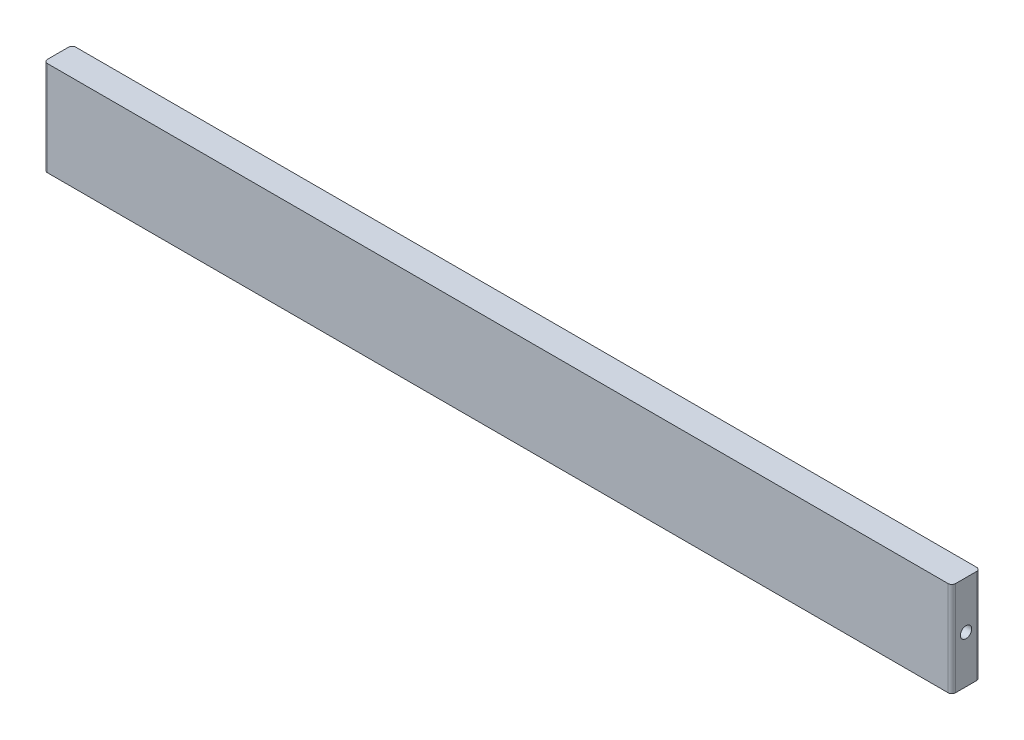
SolidWorks part; units mm, degrees
material "6061 Alloy"
ref_plane "Front Plane" through (0, 0, 0) normal (0, 0, 1) x (1, 0, 0)
ref_plane "Top Plane" through (0, 0, 0) normal (0, 1, 0) x (1, 0, 0)
ref_plane "Right Plane" through (0, 0, 0) normal (1, 0, 0) x (0, 0, -1)
sketch "Sketch1" plane through (0, -21, 0) normal (0, 1, 0) x (1, 0, 0)
  line L0 (-152.4, -170) -> (152.4, -170)
  line L4 (-152.4, 179.525) -> (-152.4, -179.525)
  line L5 (-152.4, -179.525) -> (152.4, -179.525)
  line L7 (152.4, 179.525) -> (-152.4, 179.525)
  line L9 (-152.4, -179.525) -> (152.4, -179.525)
  line L11 (152.4, 179.525) -> (-152.4, 179.525)
  line L17 (-152.4, 179.525) -> (-152.4, -179.525)
  line L23 (152.4, -179.525) -> (152.4, 179.525)
  line L24 (152.4, -179.525) -> (152.4, 179.525)
  line M6 (-152.4, 179.525) -> (-152.4, -179.525)
  line M7 (-152.4, -179.525) -> (152.4, -179.525)
  line M8 (152.4, -179.525) -> (152.4, 179.525)
  circle M23 centre (127, -174.7625) radius 2.4574
  circle M24 centre (42.3333, -174.7625) radius 2.4574
  circle M25 centre (-42.3333, -174.7625) radius 2.4574
  circle M26 centre (-127, -174.7625) radius 2.4574
  dimension "D2" = 9.525
  dimension "D1" = 0
extrude "Boss-Extrude1" add sketch "Sketch1" along normal blind 31.75 contours L0 M6 M7 M8 | M26 | M25 | M24 | M23 region at (0, -21, 174.7625) region at (127, -21, 174.7625) region at (42.3333, -21, 174.7625) region at (-42.3333, -21, 174.7625) region at (-127, -21, 174.7625)
hole_wizard "#10-24 Tapped Hole1" positions "Sketch2" profile "Sketch3" tap size "#10-24" standard "ANSI Inch"
sketch "Sketch2" plane through (0, -21, 0) normal (0, -1, 0) x (-1, 0, 0)
  point P0 (-127, -174.7625)
  point P3 (-42.3333, -174.7625)
  point P6 (127, -174.7625)
  point P9 (42.3333, -174.7625)
sketch "Sketch3" plane through (127, -21, 174.7625) normal (1, 0, 0) x (0, 0, -1)
  line L0 (0, 0) -> (0, 20.1908)
  line L1 (0, 20.1908) -> (1.8986, 19.05)
  line L2 (1.8986, 19.05) -> (1.8986, 0)
  line L5 (1.8986, 0) -> (0, 0)
  line L10 (0, 20.1908) -> (-1.8987, 19.05) construction
  line L11 (0, -6.35) -> (0, 107.95) construction
  dimension "Tap Drill Dia." = 3.7973
  dimension "Tap Drill Depth" = 19.05
  dimension "Drill Angle" = 118
cosmetic thread "Hole Thread1" parameters "D1"=15.24, "D2"=4.826
cosmetic thread "Hole Thread2" parameters "D1"=15.24, "D2"=4.826
cosmetic thread "Hole Thread3" parameters "D1"=15.24, "D2"=4.826
cosmetic thread "Hole Thread4" parameters "D1"=15.24, "D2"=4.826
hole_wizard "#10-24 Tapped Hole2" positions "Sketch4" profile "Sketch5" tap size "#10-24" standard "ANSI Inch"
sketch "Sketch4" plane through (152.4, 0, 0) normal (1, 0, 0) x (0, 0, -1)
  point P0 (-174.7625, -5.125)
sketch "Sketch5" plane through (152.4, -5.125, 174.7625) normal (0, 1, 0) x (0, 0, -1)
  line L0 (0, 0) -> (0, 20.1908)
  line L1 (0, 20.1908) -> (1.8986, 19.05)
  line L2 (1.8986, 19.05) -> (1.8986, 0)
  line L5 (1.8986, 0) -> (0, 0)
  line L10 (0, 20.1908) -> (-1.8986, 19.05) construction
  line L11 (0, -6.35) -> (0, 107.95) construction
  dimension "Tap Drill Dia." = 3.7973
  dimension "Tap Drill Depth" = 19.05
  dimension "Drill Angle" = 118
cosmetic thread "Hole Thread5" parameters "D1"=15.24, "D2"=4.826
mirror "Mirror1" about plane through (0, 0, 0) normal (1, 0, 0) of "#10-24 Tapped Hole2"
cosmetic thread "Hole Thread6" parameters "D1"=15.24, "D2"=4.826
fillet "Fillet1" radius 1.27 4 edges at (152.4, -5.125, 170) (152.4, -5.125, 179.525) (-152.4, -5.125, 170) (-152.4, -5.125, 179.525)
